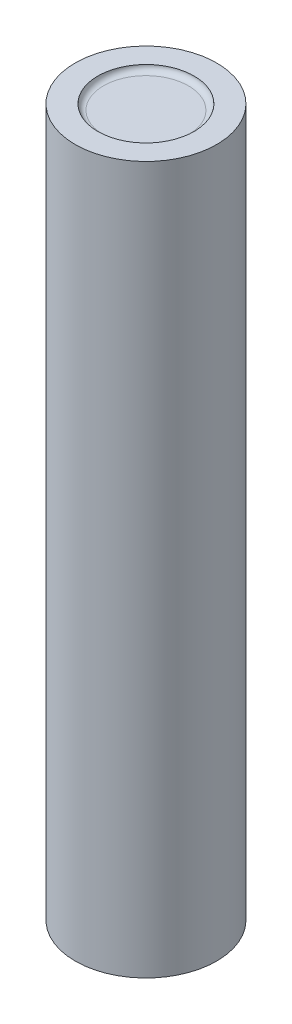
SolidWorks part; units mm, degrees
ref_plane "前视基准面" through (0, 0, 0) normal (0, 0, 1) x (1, 0, 0)
ref_plane "上视基准面" through (0, 0, 0) normal (0, 1, 0) x (1, 0, 0)
ref_plane "右视基准面" through (0, 0, 0) normal (1, 0, 0) x (0, 0, -1)
other "Configuration Table"
sketch "草图1" plane through (0, 0, 0) normal (0, 1, 0) x (1, 0, 0)
  circle A0 centre (0, 0) radius 12.5
  dimension "D1" = 25
extrude "凸台-拉伸1" add sketch "草图1" along normal blind 125
sketch "草图2" plane through (0, 0, 0) normal (0, 1, 0) x (1, 0, 0)
  circle A0 centre (0, 0) radius 5
  dimension "D1" = 10
extrude "凸台-拉伸2" add sketch "草图2" against normal blind 5
fillet "圆角1" radius 1 1 edges at (0, -5, 5)
ref_plane "基准面1" through (0, 125, 0) normal (0, 1, 0) x (1, 0, 0)
sketch "草图3" plane through (0, 125, 0) normal (0, 1, 0) x (1, 0, 0)
  circle A0 centre (0, 0) radius 8.5
extrude "切除-拉伸1" cut sketch "草图3" against normal blind 1
fillet "圆角2" radius 1 1 edges at (0, 124, 8.5)
